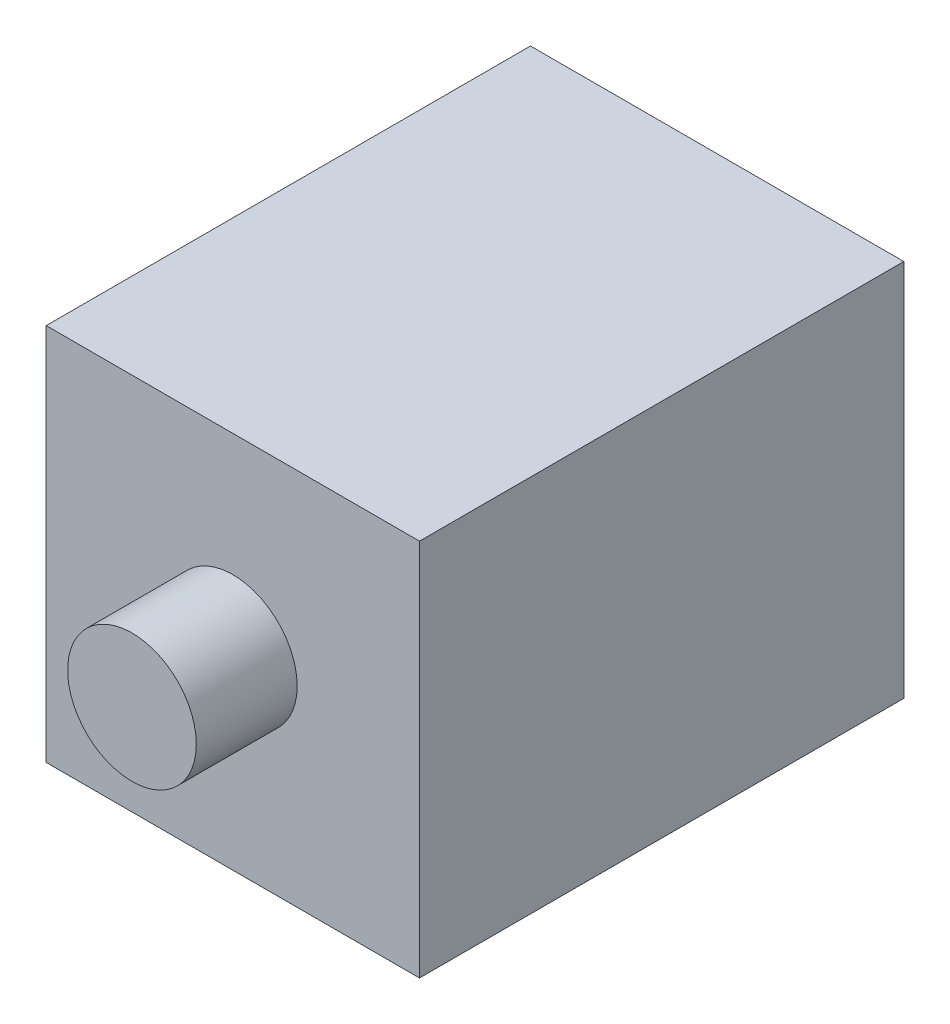
SolidWorks part; units mm, degrees
ref_plane "Plan de face" through (0, 0, 0) normal (0, 0, 1) x (1, 0, 0)
ref_plane "Plan de dessus" through (0, 0, 0) normal (0, 1, 0) x (1, 0, 0)
ref_plane "Plan de droite" through (0, 0, 0) normal (1, 0, 0) x (0, 0, -1)
sketch "Esquisse1" plane through (0, 0, 0) normal (0, 0, 1) x (1, 0, 0)
  line L2 (0, 0) -> (37, 0)
  line L3 (0, 0) -> (0, 37.5)
  line L4 (0, 37.5) -> (37, 37.5)
  line L5 (37, 0) -> (37, 37.5)
  dimension "D1" = 37.5
  dimension "D2" = 37
extrude "Boss.-Extru.1" add sketch "Esquisse1" along normal blind 48
sketch "Esquisse2" plane through (0, 0, 48) normal (0, 0, 1) x (1, 0, 0)
  line L0 (37, 0) -> (37, 37.5) construction
  line L4 (37, 37.5) -> (0, 37.5) construction
  circle A0 centre (18.5, 19) radius 6.375
  dimension "D3" = 12.75
  dimension "D1" = 18.5
  dimension "D2" = 18.5
extrude "Boss.-Extru.2" add sketch "Esquisse2" along normal blind 10
sketch "Esquisse3" plane through (0, 0, 48) normal (0, 0, 1) x (1, 0, 0)
  line L0 (37, 37.5) -> (0, 37.5) construction
  line L1 (0, 37.5) -> (0, 0) construction
  line L2 (37, 0) -> (37, 37.5) construction
  line L3 (0, 0) -> (37, 0) construction
  circle A0 centre (5, 32.5) radius 1.5
  circle A1 centre (32, 32.5) radius 1.5
  circle A2 centre (32, 5) radius 1.5
  circle A3 centre (5, 5) radius 1.5
  dimension "D3" = 3
  dimension "D5" = 3
  dimension "D9" = 3
  dimension "D11" = 3
  dimension "D1" = 5
  dimension "D2" = 5
  dimension "5" = 5
  dimension "D4" = 5
  dimension "D6" = 5
  dimension "D7" = 5
  dimension "D8" = 5
  dimension "D10" = 5
